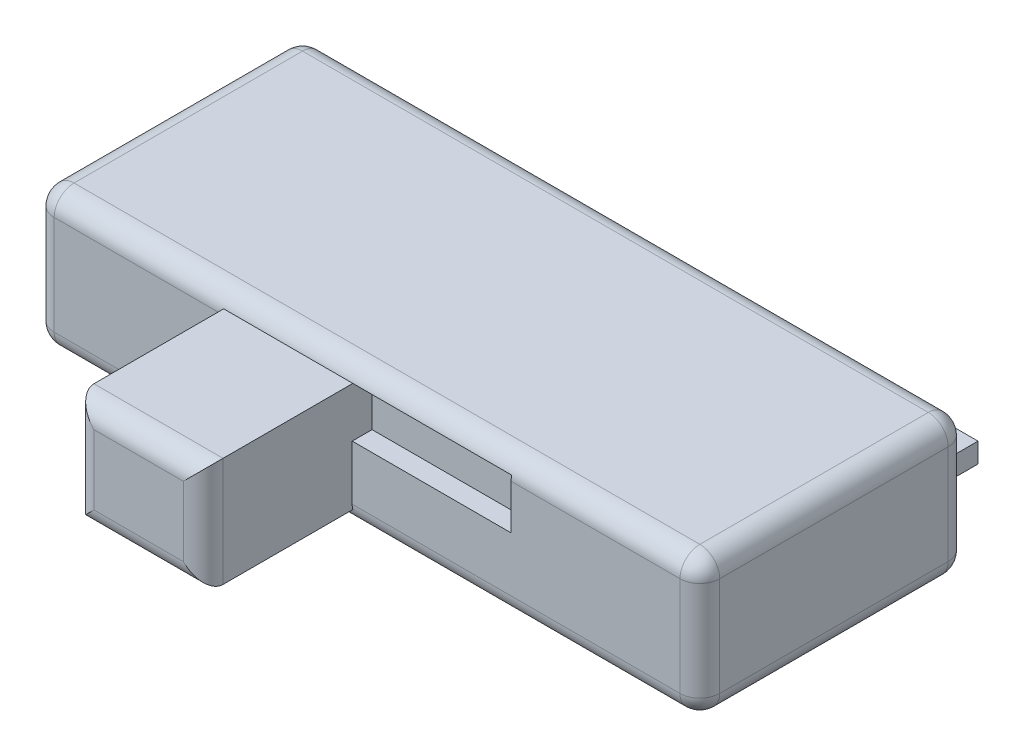
SolidWorks part; units mm, degrees
material "Настроенная пользователем пластмасса"
ref_plane "Спереди" through (0, 0, 0) normal (0, 0, 1) x (1, 0, 0)
ref_plane "Сверху" through (0, 0, 0) normal (0, 1, 0) x (1, 0, 0)
ref_plane "Справа" through (0, 0, 0) normal (1, 0, 0) x (0, 0, -1)
sketch "Эскиз1" plane through (0, 0, 0) normal (0, 1, 0) x (1, 0, 0)
  line L1 (-3.35, -1.35) -> (3.35, -1.35)
  line L2 (-3.35, -1.35) -> (-3.35, 1.35)
  line L3 (-3.35, 1.35) -> (3.35, 1.35)
  line L4 (3.35, -1.35) -> (3.35, 1.35)
  line L5 (-3.35, -1.35) -> (3.35, 1.35) construction
  line L6 (-3.35, 1.35) -> (3.35, -1.35) construction
  point P0 (0, 0)
  dimension "D1" = 2.7
  dimension "D2" = 6.7
extrude "Бобышка-Вытянуть1" add sketch "Эскиз1" along normal blind 1.4
sketch "Эскиз2" plane through (0, 0, 1.35) normal (0, 0, 1) x (1, 0, 0)
  line L0 (0, 0) -> (0, 1.4) construction
  line L1 (-1.45, 0.15) -> (1.45, 0.15) construction
  line L2 (-1.45, 0.15) -> (-1.45, 1.25) construction
  line L3 (-1.45, 1.25) -> (1.45, 1.25) construction
  line L4 (1.45, 0.15) -> (1.45, 1.25) construction
  line L5 (-1.45, 0.15) -> (1.45, 1.25) construction
  line L6 (-1.45, 1.25) -> (1.45, 0.15) construction
  line L7 (-3.35, 1.4) -> (3.35, 1.4) construction
  line L8 (-1.45, 1.25) -> (-1.45, 0.75)
  line L9 (-1.45, 0.75) -> (1.45, 0.75)
  line L10 (1.45, 0.75) -> (1.45, 1.25)
  line L11 (-1.45, 1.25) -> (1.45, 1.25)
  point P0 (0, 0.7)
  dimension "D1" = 1.1
  dimension "D2" = 2.9
  dimension "D3" = 0.5
extrude "Вырез-Вытянуть1" cut sketch "Эскиз2" against normal blind 0.2
sketch "Эскиз3" plane through (0, 0, 1.15) normal (0, 0, 1) x (1, 0, 0)
  line L1 (-1.45, 1.25) -> (-0.15, 1.25)
  line L2 (-1.45, 1.25) -> (-1.45, 0.15)
  line L3 (-1.45, 0.15) -> (-0.15, 0.15)
  line L4 (-0.15, 1.25) -> (-0.15, 0.15)
  dimension "D1" = 1.3
  dimension "D2" = 1.1
extrude "Бобышка-Вытянуть2" add sketch "Эскиз3" along normal blind 1.7
sketch "Эскиз4" plane through (0, 0, 0) normal (0, -1, 0) x (1, 0, 0)
  line L0 (3.35, -1.35) -> (-3.35, -1.35) construction
  line L1 (-2.45, -1.35) -> (-2.05, -1.35)
  line L2 (-2.45, -1.35) -> (-2.45, -2.35)
  line L3 (-2.45, -2.35) -> (-2.05, -2.35)
  line L4 (-2.05, -1.35) -> (-2.05, -2.35)
  line L5 (-2.25, -1.35) -> (-2.25, -2.35) construction
  line L6 (0.95, -1.35) -> (0.55, -1.35)
  line L7 (0.95, -1.35) -> (0.95, -2.35)
  line L8 (0.95, -2.35) -> (0.55, -2.35)
  line L9 (0.55, -1.35) -> (0.55, -2.35)
  line L10 (2.45, -1.35) -> (2.05, -1.35)
  line L11 (2.45, -1.35) -> (2.45, -2.35)
  line L12 (2.45, -2.35) -> (2.05, -2.35)
  line L13 (2.05, -1.35) -> (2.05, -2.35)
  line L14 (0.75, -1.35) -> (0.75, -2.35) construction
  line L15 (2.25, -1.35) -> (2.25, -2.35) construction
  dimension "D1" = 3
  dimension "D2" = 1.5
  dimension "D3" = 0.4
  dimension "D4" = 2.25
  dimension "D5" = 1
extrude "Бобышка-Вытянуть3" add sketch "Эскиз4" against normal blind 0.2
sketch "Эскиз6" plane through (0, 0, 0) normal (0, -1, 0) x (1, 0, 0)
  line L0 (-1.5, 0) -> (1.5, 0) construction
  circle A0 centre (-1.5, 0) radius 0.35
  circle A1 centre (1.5, 0) radius 0.35
  dimension "D1" = 0.7
  dimension "D2" = 3
extrude "Бобышка-Вытянуть4" add sketch "Эскиз6" along normal blind 0.5
fillet "Скругление1" radius 0.2 19 edges at (3.35, 0.7, 1.35) (3.35, 1.4, 0) (3.35, 0.7, -1.35) (3.35, 0, 0) (-3.35, 0.7, -1.35) (-3.35, 1.4, 0) (-3.35, 0.7, 1.35) (-3.35, 0, 0) (2.9, 0, -1.35) (1.5, 0, -1.35) (-0.75, 0, -1.35) (-2.9, 0, -1.35) (0, 1.4, -1.35) (0, 1.4, 1.35) (0, 0, 1.35) (-0.8, 1.25, 2.85) (-0.15, 0.7, 2.85) (-0.8, 0.15, 2.85) (-1.45, 0.7, 2.85)
chamfer "Фаска1" distance 0.2 angle 45 2 edges at (1.5, -0.5, -0.35) (-1.5, -0.5, -0.35)
